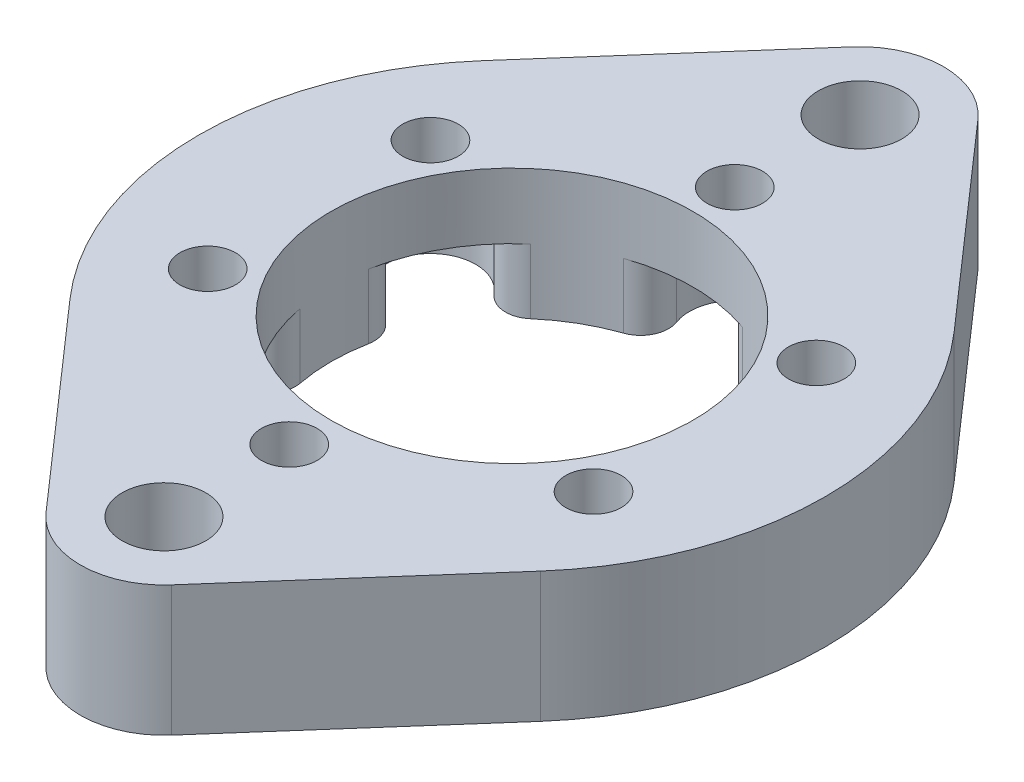
SolidWorks part; units mm, degrees
ref_plane "Front Plane" through (0, 0, 0) normal (0, 0, 1) x (1, 0, 0)
ref_plane "Top Plane" through (0, 0, 0) normal (0, 1, 0) x (1, 0, 0)
ref_plane "Right Plane" through (0, 0, 0) normal (1, 0, 0) x (0, 0, -1)
ref_axis "Axis1" through (0, -54.0054, 0) along (0, 1, 0)
sketch "Sketch1" plane through (0, 0, 0) normal (0, 1, 0) x (1, 0, 0)
  line L0 (0, 13) -> (0, 19) construction
  line L1 (-4.5076, 28.96) -> (-16.9035, 14.85)
  line L3 (-13, 0) -> (13, 0) construction
  line L5 (-4.5076, -28.96) -> (-16.9035, -14.85)
  line L8 (4.5076, 28.96) -> (16.9035, 14.85)
  line L9 (4.5076, -28.96) -> (16.9035, -14.85)
  circle A0 centre (0, 0) radius 13
  circle A1 centre (0, 0) radius 19 construction
  circle A2 centre (0, 16) radius 2
  circle A3 centre (13.8564, 8) radius 2
  circle A4 centre (13.8564, -8) radius 2
  circle A5 centre (0, -16) radius 2
  circle A6 centre (-13.8564, -8) radius 2
  circle A7 centre (-13.8564, 8) radius 2
  circle A8 centre (0, 0) radius 25 construction
  circle A9 centre (0, 25) radius 3
  circle A10 centre (0, -25) radius 3
  arc A11 (4.5076, 28.96) -> (-4.5076, 28.96) centre (0, 25) ccw
  arc A13 (4.5076, -28.96) -> (-4.5076, -28.96) centre (0, -25) cw
  arc A14 (-16.9035, 14.85) -> (-16.9035, -14.85) centre (0, 0) ccw
  arc A15 (16.9035, -14.85) -> (16.9035, 14.85) centre (0, 0) ccw
  point P21 (0, 0)
  point P27 (0, 0)
  dimension "D1" = 38
  dimension "D2" = 26
  dimension "D3" = 4
  dimension "D5" = 50
  dimension "D6" = 6
  dimension "D8" = 22.5
  dimension "D9" = 3
  dimension "D4" = 6
  dimension "D7" = 2
extrude "Boss-Extrude1" add sketch "Sketch1" along normal blind 9.35
sketch "Sketch2" plane through (0, 9.35, 0) normal (0, 1, 0) x (1, 0, 0)
  circle A0 centre (0, 0) radius 19 construction
  circle A1 centre (0, 0) radius 19
extrude "Cut-Extrude1" [suppressed] cut sketch "Sketch2" against normal blind 3.175
ref_plane "Plane1" through (0, 4.65, 0) normal (0, 1, 0) x (1, 0, 0)
sketch "Sketch3" plane through (0, 0, 0) normal (0, -1, 0) x (1, 0, 0)
  circle A0 centre (0, -16) radius 3.25
  circle A1 centre (-13.8564, -8) radius 3.25
  circle A2 centre (-13.8564, 8) radius 3.25
  circle A3 centre (0, 16) radius 3.25
  circle A4 centre (13.8564, 8) radius 3.25
  circle A5 centre (13.8564, -8) radius 3.25
  point P16 (0, 0)
  dimension "D2" = 6.5
  dimension "D1" = 6
extrude "Cut-Extrude2" cut sketch "Sketch3" against normal up to surface (4.65 mm away) up to plane "Plane1"
fillet "Fillet1" radius 2 12 edges at (1.1257, 2.325, -12.9512) (-1.1257, 2.325, -12.9512) (-10.6532, 2.325, -7.4505) (-11.7789, 2.325, -5.5007) (-11.7789, 2.325, 5.5007) (-10.6532, 2.325, 7.4505) (-1.1257, 2.325, 12.9512) (1.1257, 2.325, 12.9512) (10.6532, 2.325, 7.4505) (11.7789, 2.325, 5.5007) (10.6532, 2.325, -7.4505) (11.7789, 2.325, -5.5007)
